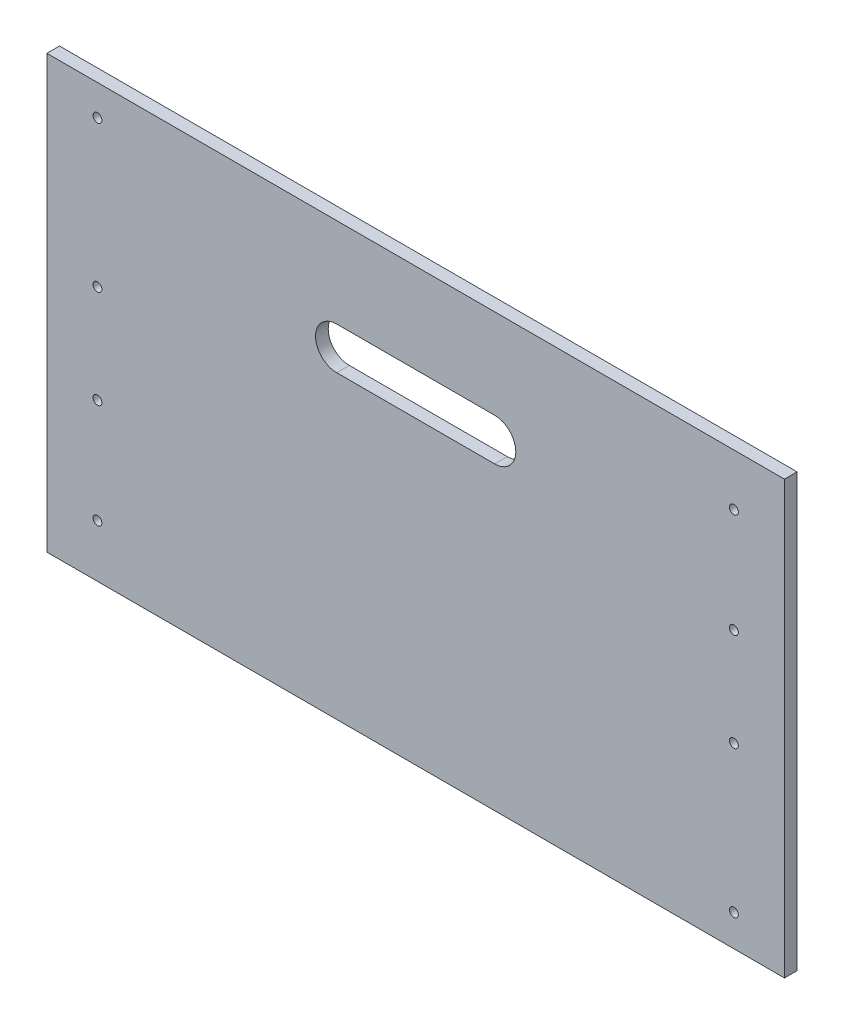
SolidWorks part; units mm, degrees
material "Acrílico (médio-alto impacto)"
ref_plane "Plano frontal" through (0, 0, 0) normal (0, 0, 1) x (1, 0, 0)
ref_plane "Plano superior" through (0, 0, 0) normal (0, 1, 0) x (1, 0, 0)
ref_plane "Plano direito" through (0, 0, 0) normal (1, 0, 0) x (0, 0, -1)
sketch "Esboço1" plane through (0, 0, 0) normal (0, 0, 1) x (1, 0, 0)
  line L5 (-175, -102.5) -> (175, -102.5)
  line L6 (-175, -102.5) -> (-175, 102.5)
  line L11 (-175, 102.5) -> (175, 102.5)
  line L25 (175, -102.5) -> (175, 102.5)
  line L26 (-175, -102.5) -> (175, 102.5) construction
  line L27 (-175, 102.5) -> (175, -102.5) construction
  point P0 (0, 0)
  dimension "D1" = 350
  dimension "D2" = 205
extrude "Ressalto-extrusão1" add sketch "Esboço1" along normal blind 6 contours L5 L25 L11 L6 region at (0, 0, 0)
sketch "Esboço2" plane through (0, 0, 6) normal (0, 0, 1) x (1, 0, 0)
  line L0 (-37.5, 50) -> (37.5, 50) construction
  line L1 (-37.5, 60) -> (37.5, 60)
  line L2 (-37.5, 40) -> (37.5, 40)
  line L3 (-175, 102.5) -> (175, 102.5) construction
  arc A0 (-37.5, 60) -> (-37.5, 40) centre (-37.5, 50) ccw
  arc A1 (37.5, 40) -> (37.5, 60) centre (37.5, 50) ccw
  point P2 (0, 50)
  dimension "D3" = 10
  dimension "D1" = 75
  dimension "D2" = 50
  dimension "D4" = 75
extrude "Corte-extrusão1" cut sketch "Esboço2" against normal through all
hole_wizard "Furo de diâmetro Ø4.2 (4.2)1" positions "Esboço3" profile "Esboço4" hole size "Ø4.2" standard "ISO" end condition through all
sketch "Esboço3" plane through (0, 0, 0) normal (0, 0, -1) x (-1, 0, 0)
  point P0 (-151, -87.5)
  point P3 (-151, -18)
  point P6 (-151, 28.5)
  point P9 (-151, 78)
  point P12 (151, -77.5)
  point P15 (151, -28)
  point P18 (151, 18.5)
  point P21 (151, 88)
sketch "Esboço4" plane through (151, -87.5, 0) normal (1, 0, 0) x (0, 1, 0)
  line L0 (0, 0) -> (0, 6)
  line L1 (0, 6) -> (2.1, 6)
  line L2 (2.1, 6) -> (2.1, 0)
  line L5 (2.1, 0) -> (0, 0)
  line L11 (0, -6.35) -> (0, 107.95) construction
  dimension "Thru Hole Dia." = 4.2
  dimension "Thru Hole Depth" = 6
